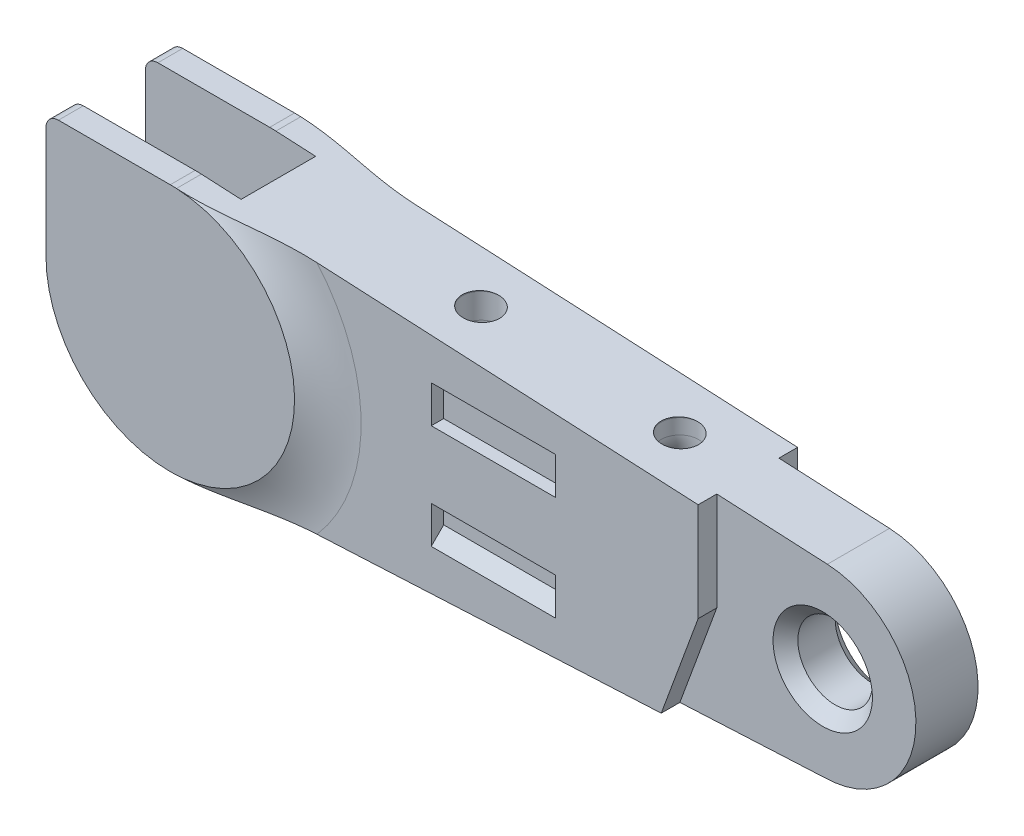
SolidWorks part; units mm, degrees
ref_plane "Front Plane" through (0, 0, 0) normal (0, 0, 1) x (1, 0, 0)
ref_plane "Top Plane" through (0, 0, 0) normal (0, 1, 0) x (1, 0, 0)
ref_plane "Right Plane" through (0, 0, 0) normal (1, 0, 0) x (0, 0, -1)
sketch "Sketch1" plane through (0, 0, 0) normal (0, 0, 1) x (1, 0, 0)
  line L0 (55, 0) -> (-55, 0) construction
  line L1 (0, -55) -> (0, 55) construction
  line L2 (-24.5, 9.9875) -> (25.375, 7.4906)
  line L3 (-25, -10) -> (25, -7.5)
  line L4 (-25, 10) -> (-34, 10)
  line L5 (-35, 9) -> (-35, 0)
  arc A0 (-35, 0) -> (-25, 10) centre (-25, 0) ccw
  circle A1 centre (25, 0) radius 7.5
  circle A2 centre (-25, 0) radius 2.5
  circle A3 centre (25, 0) radius 3
  arc A4 (-34, 10) -> (-35, 9) centre (-34, 9) ccw
  dimension "D1" = 20
  dimension "D2" = 15
  dimension "D5" = 5
  dimension "D6" = 6
  dimension "D7" = 1
  dimension "D3" = 50
  dimension "D4" = 25
extrude "Boss-Extrude1" add sketch "Sketch1" along normal mid plane 8 contours A1 L2 A0 L3 region at (0.4605, 0.0075, 0)
extrude "Boss-Extrude2" add sketch "Sketch1<3>" along normal mid plane 10 contours A0 L3 A2 region at (-15.2859, 0.2424, 0)
sketch "Sketch1<3>" plane through (0, 0, 0) normal (0, 0, 1) x (1, 0, 0) same geometry as "Sketch1"
extrude "Boss-Extrude3" add sketch "Sketch1<5>" along normal mid plane 9 contours A1 A3 region at (30.2806, 5.0228, 0)
sketch "Sketch1<5>" plane through (0, 0, 0) normal (0, 0, 1) x (1, 0, 0) same geometry as "Sketch1"
fillet "Fillet1" radius 10 2 edges at (-15.0031, 0.2495, -4) (-15.0031, 0.2495, 4)
extrude "Cut-Extrude2" cut sketch "Sketch1<6>" against normal mid plane 6 contours A0 L3 A2 region at (-15.2859, 0.2424, 0)
sketch "Sketch1<6>" plane through (0, 0, 0) normal (0, 0, 1) x (1, 0, 0) same geometry as "Sketch1"
sketch "Sketch2" plane through (0, 0, 0) normal (0, 0, 1) x (1, 0, 0)
  line L0 (-14.5, 0) -> (-14.5, -10.5)
  line L1 (-14.5, -10.5) -> (-25, -10.5)
  line L2 (16.4759, 0) -> (13, -9.4488)
  line L3 (13, -9.4488) -> (25, -9.4488)
  line L4 (25, -9.4488) -> (25, -8)
  line L5 (16.4759, 0) -> (16.0501, 0)
  line L6 (55, 0) -> (-55, 0) construction
  line L7 (16.4759, 0) -> (16.4759, 8.8777)
  line L8 (16.4759, 8.8777) -> (25, 8)
  arc A0 (-14.5, 0) -> (-25, -10.5) centre (-25, 0) ccw
  arc A1 (25, -8) -> (25, 8) centre (25, 0) ccw
  dimension "D1" = 21
  dimension "D2" = 16
  dimension "D3" = 12
extrude "Cut-Extrude3" cut sketch "Sketch2" against normal mid plane 6 contours L0 A0 L1 region at (-24.4786, -0.5214, 0)
extrude "Cut-Extrude4" cut sketch "Sketch2<3>" along normal blind 7.5 from offset 10 contours A1 region at (23.245, -0.6687, 0) offset against normal yes
sketch "Sketch2<3>" plane through (0, 0, 0) normal (0, 0, 1) x (1, 0, 0) same geometry as "Sketch2"
mirror "Mirror1" about plane through (0, 0, 0) normal (0, 0, 1) of "Cut-Extrude4"
sketch "Sketch3" plane through (0, 0, 0) normal (0, 0, 1) x (1, 0, 0)
  line L0 (-5, 9.0113) -> (-5, 7)
  line L1 (-14.2086, 9.4723) -> (-24.5, 9.9875) construction
  line L2 (-2, 4) -> (8, 4)
  line L3 (11, 7) -> (11, 8.2103)
  line L4 (-14.2086, 9.4723) -> (16.4759, 7.9361) construction
  line L5 (-5, 9.0113) -> (-5, 11.3767)
  line L7 (11, 8.2103) -> (11, 10.9782)
  line L8 (0, -55) -> (0, 55) construction
  line L9 (55, 0) -> (-55, 0) construction
  arc A2 (11, 7) -> (8, 4) centre (8, 7) cw
  arc A3 (-2, 4) -> (-5, 7) centre (-2, 7) cw
  point P24 (11, 4)
  point P27 (-5, 4)
  dimension "D1" = 16
  dimension "D2" = 5
  dimension "D3" = 4
sweep "Cut-Sweep5" cut path "Sketch3" circular profile diameter 3 parameters "D3"=3
mirror "Mirror2" about plane through (0, 0, 0) normal (0, 1, 0) of "Cut-Sweep5"
extrude "Boss-Extrude4" add sketch "Sketch1<7>" along normal mid plane 10 contours A2 region at (-25, 0, 0)
sketch "Sketch1<7>" plane through (0, 0, 0) normal (0, 0, 1) x (1, 0, 0) same geometry as "Sketch1"
chamfer "Chamfer1" distance 1 angle 45 4 edges at (28, 0, -2.5) (22, 0, 2.5) (-22.5, 0, 3) (-22.5, 0, -3)
sketch "Sketch139" plane through (0, 0, 0) normal (1, 0, 0) x (0, 0, -1)
  line L0 (4, 8.7042) -> (4, 5.7042)
  line L1 (4, 9.4723) -> (4, 7.9361) construction
  line L2 (4, 7.9361) -> (4, 0) construction
  line L3 (4, 5.7042) -> (3, 4.7042)
  line L4 (3, 4.7042) -> (3, 2.7042)
  line L5 (3, 2.7042) -> (5.5203, 2.7042)
  line L6 (5.5203, 2.7042) -> (5.5203, 8.7042)
  line L7 (5.5203, 8.7042) -> (4, 8.7042)
  dimension "D1" = 3
  dimension "D2" = 1
  dimension "D3" = 1
  dimension "D4" = 2
extrude "Cut-Extrude5" cut sketch "Sketch139" against normal mid plane 10
mirror "Mirror3" about plane through (0, 0, 0) normal (0, 1, 0) of "Cut-Extrude5"
mirror "Mirror4" about plane through (0, 0, 0) normal (0, 0, 1) of "Mirror3"
